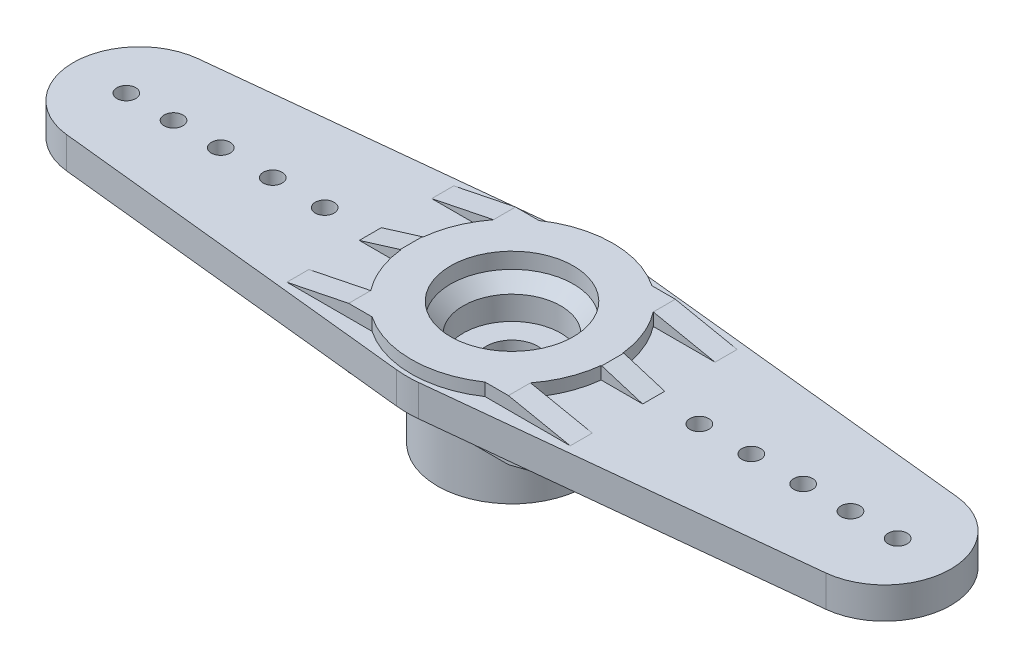
SolidWorks part; units mm, degrees
material "PA Type 6"
ref_plane "Plan de face" through (0, 0, 0) normal (0, 0, 1) x (1, 0, 0)
ref_plane "Plan de dessus" through (0, 0, 0) normal (0, 1, 0) x (1, 0, 0)
ref_plane "Plan de droite" through (0, 0, 0) normal (1, 0, 0) x (0, 0, -1)
ref_axis "Axe1" through (0, 0, 0) along (0, 1, 0)
sketch "Esquisse1" plane through (0, 0, 0) normal (0, 1, 0) x (1, 0, 0)
  line L0 (-27.87, 0) -> (27.87, 0) construction
  line L1 (0, 0) -> (0, -8.9896) construction
  line L2 (-24.1083, 4.1771) -> (-0.696, 6.6336)
  line L3 (-24.1083, -4.1771) -> (-0.696, -6.6336)
  line L4 (24.1083, -4.1771) -> (0.696, -6.6336)
  line L5 (24.1083, 4.1771) -> (0.696, 6.6336)
  line L6 (-9, -3.9) -> (-5.0744, -3.9)
  line L7 (-9, 5.3) -> (-3.5875, 5.3)
  line L8 (-9, 5.3) -> (-9, 3.9)
  line L9 (-9, 3.9) -> (-5.0744, 3.9)
  line L10 (-9, -5.3) -> (-9, -3.9)
  line L11 (-9, 0.7) -> (-6.3616, 0.7)
  line L12 (-9, 0.7) -> (-9, -0.7)
  line L13 (-9, -0.7) -> (-6.3616, -0.7)
  line L14 (-9, -5.3) -> (-3.5875, -5.3)
  circle A0 centre (0, 0) radius 27.87 construction
  circle A1 centre (0, 0) radius 6.67
  arc A2 (-24.1083, 4.1771) -> (-24.1083, -4.1771) centre (-23.67, 0) ccw
  circle A4 centre (-21.5, 0) radius 0.6
  circle A5 centre (-18.5, 0) radius 0.6
  circle A6 centre (-15.2, 0) radius 0.6
  circle A7 centre (11.9, 0) radius 0.6
  circle A8 centre (15.2, 0) radius 0.6
  circle A9 centre (18.5, 0) radius 0.6
  circle A10 centre (21.5, 0) radius 0.6
  arc A11 (24.1083, 4.1771) -> (24.1083, -4.1771) centre (23.67, 0) cw
  circle A13 centre (0, 0) radius 1.65
  circle A14 centre (0, 0) radius 3.1
  circle A16 centre (-24.5, 0) radius 0.6
  circle A17 centre (-11.9, 0) radius 0.6
  circle A18 centre (24.5, 0) radius 0.6
  circle A19 centre (0, 0) radius 6.4
  circle A20 centre (0, 0) radius 3.9
  dimension "D1" = 55.74
  dimension "D2" = 13.34
  dimension "D3" = 4.2
  dimension "D9" = 7.8
  dimension "D10" = 6.2
  dimension "D11" = 1.4
  dimension "D12" = 3.3
  dimension "D7" = 12.8
  dimension "D5" = 1.2
  dimension "D4" = 49
  dimension "D6" = 3
  dimension "D8" = 3
  dimension "D13" = 3.3
  dimension "D14" = 3.3
  dimension "D15" = 18
  dimension "D16" = 10.6
  dimension "D17" = 1.4
sketch "Esquisse2" plane through (0, 0, 0) normal (0, 0, 1) x (1, 0, 0)
  line L0 (0, 3.9296) -> (0, -5.2174) construction
  line L1 (7.337, 0) -> (-7.337, 0) construction
  line L2 (0, -3.5) -> (-4.735, -3.5)
  line L3 (0, -3.5) -> (0, 4.3)
  line L4 (0, 4.3) -> (-6.4, 4.3)
  line L5 (-4.735, -3.5) -> (-4.735, 1.5)
  line L6 (-6.4, 4.3) -> (-6.4, 1.5)
  line L9 (-6.4, 1.5) -> (-4.735, 1.5)
  point P9 (-4.735, 1.5)
  point P10 (-4.735, 3.5)
  point P13 (-6.4, 0)
  dimension "D1" = 9.47
  dimension "D2" = 3.5
  dimension "D3" = 7.8
  dimension "D4" = 5
  dimension "D5" = 2
revolve "Révolution1" add sketch "Esquisse2" angle 360 about L0
ref_plane "Plan1" through (0, 3.5, 0) normal (0, 1, 0) x (1, 0, 0)
sketch "Esquisse3" plane through (0, 3.5, 0) normal (0, 1, 0) x (1, 0, 0)
  line L0 (-24.1083, 4.1771) -> (-0.696, 6.6336) construction
  line L1 (-24.1083, -4.1771) -> (-0.696, -6.6336) construction
  line L2 (-24.1083, 4.1771) -> (-0.696, 6.6336)
  line L3 (-24.1083, -4.1771) -> (-0.696, -6.6336)
  line L4 (0, 0) -> (0, -8.9896) construction
  line L5 (0, 0) -> (0, -8.9896) construction
  line L6 (24.1083, -4.1771) -> (0.696, -6.6336)
  line L7 (24.1083, 4.1771) -> (0.696, 6.6336)
  arc A0 (-24.1083, 4.1771) -> (-24.1083, -4.1771) centre (-23.67, 0) ccw construction
  circle A2 centre (-21.5, 0) radius 0.6 construction
  circle A3 centre (-18.5, 0) radius 0.6 construction
  circle A4 centre (-15.2, 0) radius 0.6 construction
  circle A5 centre (0, 0) radius 6.67 construction
  arc A6 (-24.1083, 4.1771) -> (-24.1083, -4.1771) centre (-23.67, 0) ccw
  circle A7 centre (-24.5, 0) radius 0.6 construction
  circle A8 centre (-21.5, 0) radius 0.6
  circle A9 centre (-18.5, 0) radius 0.6
  circle A10 centre (-15.2, 0) radius 0.6
  arc A11 (-0.696, -6.6336) -> (0.696, -6.6336) centre (0, 0) ccw
  circle A12 centre (15.2, 0) radius 0.6
  circle A13 centre (18.5, 0) radius 0.6
  circle A14 centre (21.5, 0) radius 0.6
  circle A15 centre (-24.5, 0) radius 0.6
  arc A16 (24.1083, 4.1771) -> (24.1083, -4.1771) centre (23.67, 0) cw
  arc A17 (0.696, 6.6336) -> (-0.696, 6.6336) centre (0, 0) ccw
  circle A18 centre (-11.9, 0) radius 0.6 construction
  circle A19 centre (-11.9, 0) radius 0.6
  circle A20 centre (11.9, 0) radius 0.6
  circle A21 centre (24.5, 0) radius 0.6
extrude "Boss.-Extru.1" add sketch "Esquisse3" against normal up to vertex (2 mm away) up to point (-4.735, 1.5, 0)
sketch "Esquisse10" plane through (0, 4.3, 0) normal (0, 1, 0) x (1, 0, 0)
  line L0 (-9, 5.3) -> (-3.5875, 5.3) construction
  line L1 (-9, 5.3) -> (-9, 3.9) construction
  line L2 (-9, 3.9) -> (-5.0744, 3.9) construction
  line L3 (-9, 0.7) -> (-6.3616, 0.7) construction
  line L4 (-9, 0.7) -> (-9, -0.7) construction
  line L5 (-9, -0.7) -> (-6.3616, -0.7) construction
  line L6 (-9, -3.9) -> (-5.0744, -3.9) construction
  line L7 (-9, -5.3) -> (-9, -3.9) construction
  line L8 (-9, -5.3) -> (-3.5875, -5.3) construction
  line L9 (-9, 5.3) -> (-3.5875, 5.3)
  line L10 (-9, 5.3) -> (-9, 3.9)
  line L11 (-9, 3.9) -> (-5.0744, 3.9)
  line L12 (-9, 0.7) -> (-6.3616, 0.7)
  line L13 (-9, 0.7) -> (-9, -0.7)
  line L14 (-9, -0.7) -> (-6.3616, -0.7)
  line L15 (-9, -3.9) -> (-5.0744, -3.9)
  line L16 (-9, -5.3) -> (-9, -3.9)
  line L17 (-9, -5.3) -> (-3.5875, -5.3)
  line L18 (0, 0) -> (0, -8.9896) construction
  line L19 (0, 0) -> (0, -8.9896) construction
  line L20 (9, -5.3) -> (3.5875, -5.3)
  line L21 (9, -5.3) -> (9, -3.9)
  line L22 (9, -3.9) -> (5.0744, -3.9)
  line L23 (9, -0.7) -> (6.3616, -0.7)
  line L24 (9, 0.7) -> (9, -0.7)
  line L25 (9, 0.7) -> (6.3616, 0.7)
  line L26 (9, 3.9) -> (5.0744, 3.9)
  line L27 (9, 5.3) -> (9, 3.9)
  line L28 (9, 5.3) -> (3.5875, 5.3)
  circle A0 centre (0, 0) radius 6.4 construction
  arc A1 (-3.5875, 5.3) -> (-5.0744, 3.9) centre (0, 0) ccw
  arc A2 (-6.3616, 0.7) -> (-6.3616, -0.7) centre (0, 0) ccw
  arc A3 (-5.0744, -3.9) -> (-3.5875, -5.3) centre (0, 0) ccw
  arc A4 (3.5875, -5.3) -> (5.0744, -3.9) centre (0, 0) ccw
  arc A5 (6.3616, -0.7) -> (6.3616, 0.7) centre (0, 0) ccw
  arc A6 (5.0744, 3.9) -> (3.5875, 5.3) centre (0, 0) ccw
extrude "Boss.-Extru.2" add sketch "Esquisse10" against normal up to surface (0.8 mm away) up to face at (0, 3.5, 6.4)
sketch "Esquisse11" plane through (0, 0, -3.9) normal (0, 0, 1) x (1, 0, 0)
  line L0 (-5.0744, 4.3) -> (-9, 3.5)
  line L1 (-9, 3.5) -> (-9, 4.3)
  line L2 (-9, 4.3) -> (-5.0744, 4.3)
  line L3 (0, 0) -> (0, 2.9212) construction
  line L4 (9, 4.3) -> (5.0744, 4.3)
  line L5 (9, 3.5) -> (9, 4.3)
  line L6 (5.0744, 4.3) -> (9, 3.5)
extrude "Enlèv. mat.-Extru.6" cut sketch "Esquisse11" against normal through all
sketch "Esquisse12" plane through (0, 0, 3.9) normal (0, 0, -1) x (-1, 0, 0)
  line L3 (-5.0744, 4.3) -> (-9, 4.3)
  line L4 (-9, 3.5) -> (-5.0744, 4.3)
  line L5 (-9, 4.3) -> (-9, 3.5)
  line L6 (-5.0744, 4.3) -> (-9, 4.3)
  line L7 (-9, 3.5) -> (-5.0744, 4.3)
  line L8 (-9, 4.3) -> (-9, 3.5)
  line L9 (5.0744, 4.3) -> (9, 3.5)
  line L10 (9, 3.5) -> (9, 4.3)
  line L11 (9, 4.3) -> (5.0744, 4.3)
  line L12 (5.0744, 4.3) -> (9, 3.5)
  line L13 (9, 3.5) -> (9, 4.3)
  line L14 (9, 4.3) -> (5.0744, 4.3)
  dimension "D1" = 0
  dimension "D2" = 0
extrude "Enlèv. mat.-Extru.7" cut sketch "Esquisse12" against normal through all
sketch "Esquisse13" plane through (0, 0, 0) normal (0, 0, 1) x (1, 0, 0)
  line L0 (-6.4, 4.3) -> (-9, 3.5)
  line L1 (-9, 3.5) -> (-9, 4.3)
  line L2 (-6.4, 4.3) -> (-9, 4.3)
  line L3 (-9, 3.5) -> (-9, 4.3) construction
  line L4 (-6.3616, 3.5) -> (-9, 3.5) construction
  line L5 (-9, 4.3) -> (-6.3616, 4.3) construction
  line L8 (0, 9.8646) -> (0, 0) construction
  line L9 (6.4, 4.3) -> (9, 4.3)
  line L10 (9, 3.5) -> (9, 4.3)
  line L11 (6.4, 4.3) -> (9, 3.5)
extrude "Enlèv. mat.-Extru.8" cut sketch "Esquisse13" against normal mid plane 2
sketch "Esquisse4" plane through (0, 4.3, 0) normal (0, 1, 0) x (1, 0, 0)
  circle A1 centre (0, 0) radius 3.1
  circle A2 centre (0, 0) radius 3.1 construction
extrude "Enlèv. mat.-Extru.1" cut sketch "Esquisse4" against normal blind 3.3
sketch "Esquisse14" plane through (0, 0, 0) normal (0, 0, 1) x (1, 0, 0)
  line L0 (-3.9, 4.3) -> (-3.9, 3.3)
  line L1 (-3.9, 3.3) -> (-3.1, 2.5)
  line L2 (-3.9, 4.3) -> (0, 4.3)
  line L3 (0, 4.3) -> (0, 2.5)
  line L4 (-3.1, 2.5) -> (0, 2.5)
  line L5 (0, 4.3) -> (0, 0) construction
  line L8 (3.1, 4.3) -> (-3.1, 4.3) construction
  point P4 (-3.9, 0)
  point P11 (-3.1, 0)
  dimension "D1" = 45
  dimension "D2" = 1
revolve "Enlèvement de matière-Révolution1" cut sketch "Esquisse14" angle 360 about L5
sketch "Esquisse15" plane through (0, 1.5, 0) normal (0, -1, 0) x (1, 0, 0)
  line L0 (-9, 5.3) -> (-3.5875, 5.3) construction
  line L1 (-9, 5.3) -> (9, 5.3)
  line L2 (-9, 5.3) -> (-9, 3.9)
  line L3 (-9, 3.9) -> (9, 3.9)
  line L4 (9, 5.3) -> (9, 3.9)
  line L5 (0, 0) -> (0, 8.9896) construction
  line L6 (0, 0) -> (0, 8.9896) construction
  line L7 (-6.2802, 0) -> (6.2802, 0) construction
  line L8 (9, -5.3) -> (9, -3.9)
  line L9 (-9, -3.9) -> (9, -3.9)
  line L10 (-9, -5.3) -> (-9, -3.9)
  line L11 (-9, -5.3) -> (9, -5.3)
extrude "Boss.-Extru.3" add sketch "Esquisse15" along normal offset from surface (1 mm away) 4 up to face at (0, -3.5, 4.735)
sketch "Esquisse16" plane through (0, 0, 0) normal (0, 0, 1) x (1, 0, 0)
  line L0 (-9, 1.5) -> (-5.0744, 0.5)
  line L1 (-9, 1.5) -> (-9, 0.5)
  line L2 (-9, 0.5) -> (-5.0744, 0.5)
  line L3 (-9, 0.5) -> (-9, 1.5) construction
  line L4 (9, 0.5) -> (-9, 0.5) construction
  line L5 (9, 1.5) -> (-9, 1.5) construction
  line L6 (0, 8.0614) -> (0, 5.9493) construction
  line L7 (0, -4.29) -> (0, 4.29) construction
  line L8 (9, 0.5) -> (5.0744, 0.5)
  line L9 (9, 1.5) -> (9, 0.5)
  line L10 (9, 1.5) -> (5.0744, 0.5)
extrude "Enlèv. mat.-Extru.9" cut sketch "Esquisse16" against normal through all and the other way through all
sketch "Esquisse6" plane through (0, -3.5, 0) normal (0, -1, 0) x (1, 0, 0)
  circle A0 centre (0, 0) radius 1.65 construction
  circle A1 centre (0, 0) radius 1.65
extrude "Enlèv. mat.-Extru.3" cut sketch "Esquisse6" against normal through all
sketch "Esquisse7" plane through (0, 0, 0) normal (0, 1, 0) x (1, 0, 0)
  line L6 (0.1267, -2.9973) -> (0.2711, -2.6537)
  line L7 (0.3973, -2.6377) -> (0.6227, -2.9347)
  line L8 (0, 0) -> (0, -3.7146) construction
  line L9 (0, 0) -> (0.3388, -2.6821) construction
  arc A4 (0.1267, -2.9973) -> (0.6227, -2.9347) centre (0, 0) ccw
  arc A5 (0.3973, -2.6377) -> (0.2711, -2.6537) centre (0.3388, -2.6821) ccw
  dimension "D2" = 6
  dimension "D7" = 0.37
  dimension "D4" = 0.5
  dimension "D5" = 7.2
  dimension "D6" = 60
sketch "Esquisse8" plane through (0, 0, 0) normal (0, 1, 0) x (1, 0, 0)
  circle A0 centre (0, 0) radius 2.68
  arc A1 (0.3973, -2.6377) -> (0.2711, -2.6537) centre (0.3388, -2.6821) ccw construction
  dimension "D1" = 0.05
extrude "Enlèv. mat.-Extru.4" cut sketch "Esquisse8" against normal through all
sketch "Esquisse9" plane through (0, 0, 0) normal (0, 1, 0) x (1, 0, 0)
  line L0 (0.1267, -2.9973) -> (0.2711, -2.6537) construction
  line L2 (0.1053, -3.0482) -> (0.2656, -2.6668)
  line L3 (-0.2656, -2.6668) -> (-0.1053, -3.0482)
  line L4 (0, -2.4923) -> (0, -2.738) construction
  line L5 (0, 0) -> (0, -3.7146) construction
  arc A0 (-0.1053, -3.0482) -> (0.1053, -3.0482) centre (0, 0) ccw
  circle A1 centre (0, 0) radius 2.68
  arc A2 (-0.2656, -2.6668) -> (0.2656, -2.6668) centre (0, 0) ccw
  arc A3 (0.1267, -2.9973) -> (0.6227, -2.9347) centre (0, 0) ccw construction
  dimension "D2" = 0.05
  dimension "D1" = 0
extrude "Enlèv. mat.-Extru.5" cut sketch "Esquisse9" against normal through all
pattern_circular "Répétition circulaire1" count 25 over 360 about axis through (0, 0, 0) along (0, 1, 0) of "Enlèv. mat.-Extru.5"
